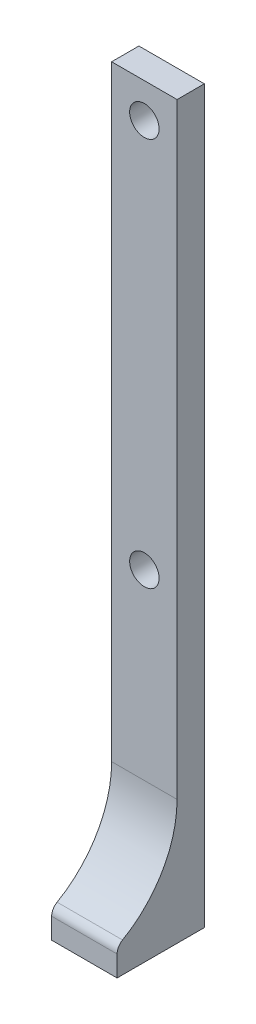
SolidWorks part; units mm, degrees
ref_plane "Přední rovina" through (0, 0, 0) normal (0, 0, 1) x (1, 0, 0)
ref_plane "Horní rovina" through (0, 0, 0) normal (0, 1, 0) x (1, 0, 0)
ref_plane "Pravá rovina" through (0, 0, 0) normal (1, 0, 0) x (0, 0, -1)
sketch "Skica2" plane through (0, 0, 0) normal (0, 0, 1) x (1, 0, 0)
  line L1 (0, 0) -> (-6, 0)
  line L2 (0, 0) -> (0, -42)
  line L3 (0, -42) -> (-6, -42)
  line L4 (-6, 0) -> (-6, -42)
  line L5 (-6, -42) -> (0, -42)
  line L6 (-6, -42) -> (-6, -67)
  line L7 (-6, -67) -> (0, -67)
  line L8 (0, -42) -> (0, -67)
  circle A0 centre (-3, -3.1638) radius 1.35
  circle A1 centre (-3, -38.8362) radius 1.35
  dimension "D5" = 2.7
  dimension "D6" = 2.7
  dimension "D1" = 6
  dimension "D2" = 42
  dimension "D3" = 3.1637
  dimension "D4" = 3
  dimension "D7" = 3.1637
  dimension "D8" = 3
  dimension "D9" = 25
extrude "Přidat vysunutím1" add sketch "Skica2" along normal blind 2.5 contours L1 L4 L3 L2 A1 A0 | L8 L3 L6 L7 region at (-3, -21, 0) region at (-3, -54.5, 0)
sketch "Skica3" plane through (0, -67, 0) normal (0, -1, 0) x (1, 0, 0)
  line L1 (0, 0) -> (-6, 0)
  line L2 (0, 0) -> (0, 8)
  line L3 (0, 8) -> (-6, 8)
  line L4 (-6, 0) -> (-6, 8)
  dimension "D1" = 6
  dimension "D2" = 8
extrude "Přidat vysunutím2" add sketch "Skica3" against normal blind 2.5
fillet "Zaoblit1" radius 10 1 edges at (-3, -64.5, 2.5)
fillet "Zaoblit2" radius 1 1 edges at (-3, -64.5, 8)
